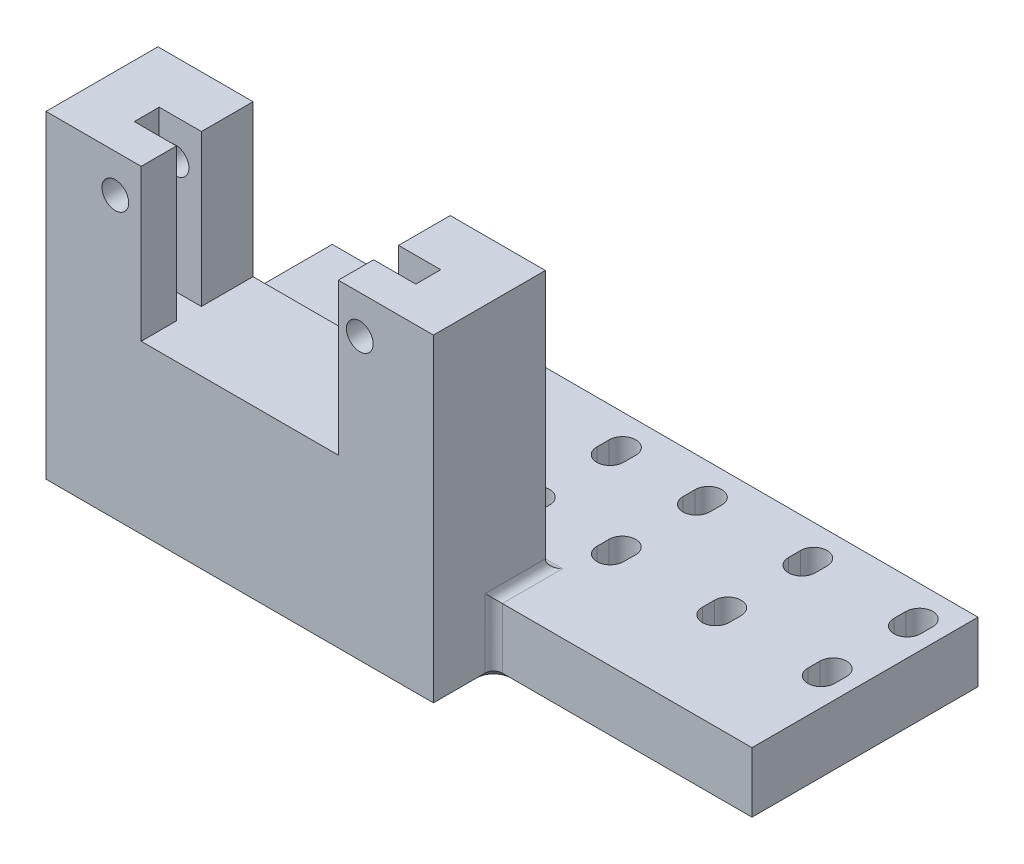
SolidWorks part; units mm, degrees
material "ABS"
ref_plane "Front Plane" through (0, 0, 0) normal (0, 0, 1) x (1, 0, 0)
ref_plane "Top Plane" through (0, 0, 0) normal (0, 1, 0) x (1, 0, 0)
ref_plane "Right Plane" through (0, 0, 0) normal (1, 0, 0) x (0, 0, -1)
sketch "Sketch1" plane through (0, 0, 0) normal (0, 1, 0) x (1, 0, 0)
  line L1 (0, 0) -> (45, 0)
  line L2 (0, 0) -> (0, 6)
  line L3 (0, 6) -> (45, 6)
  line L4 (45, 0) -> (45, 6)
  dimension "D1" = 45
  dimension "D2" = 6
extrude "Boss-Extrude1" add sketch "Sketch1" along normal blind 32
sketch "Sketch2" plane through (0, 0, 0) normal (0, 0, 1) x (1, 0, 0)
  line L0 (0, 32) -> (45, 32) construction
  line L2 (11.05, 32) -> (11.05, 14.4)
  line L3 (11.05, 14.4) -> (33.95, 14.4)
  line L4 (33.95, 32) -> (33.95, 14.4)
  line L5 (11.05, 32) -> (33.95, 32)
  line L6 (22.5, 14.4) -> (22.5, 0) construction
  line L7 (0, 0) -> (45, 0) construction
  dimension "D1" = 22.9
  dimension "D3" = 14.4
extrude "Cut-Extrude1" cut sketch "Sketch2" against normal through all
sketch "Sketch3" plane through (0, 0, 0) normal (0, -1, 0) x (1, 0, 0)
  line L0 (45, 0) -> (45, -6) construction
  line L1 (0, 0) -> (45, 0)
  line L2 (0, 0) -> (0, -24.75)
  line L3 (0, -24.75) -> (45, -24.75)
  line L4 (45, 0) -> (45, -24.75)
  dimension "D1" = 24.75
extrude "Boss-Extrude2" add sketch "Sketch3" along normal blind 6
sketch "Sketch4" plane through (45, 0, 0) normal (1, 0, 0) x (0, 0, -1)
  line L1 (24.75, 0) -> (0, 0)
  line L2 (24.75, 0) -> (24.75, -6)
  line L3 (24.75, -6) -> (0, -6)
  line L4 (0, 0) -> (0, -6)
extrude "Boss-Extrude3" add sketch "Sketch4" along normal blind 30
sketch "Sketch5" plane through (0, -6, 0) normal (0, -1, 0) x (1, 0, 0)
  line L0 (47.2888, -11.95) -> (59.5388, -11.95) construction
  line L1 (37.2888, -21.95) -> (47.2888, -21.95) construction
  line L2 (47.2888, -21.95) -> (59.5388, -21.95) construction
  line L3 (59.5388, -21.95) -> (71.7888, -21.95) construction
  line L4 (71.7888, -21.95) -> (71.7888, -11.95) construction
  line L5 (59.5388, -11.95) -> (59.5388, -21.95) construction
  line L6 (47.2888, -11.95) -> (47.2888, -21.95) construction
  line L7 (0, -24.75) -> (75, -24.75) construction
  line L8 (75, 0) -> (75, -24.75) construction
  line L9 (59.5388, -11.95) -> (71.7888, -11.95) construction
  circle A1 centre (37.2888, -21.95) radius 1.5
  circle A5 centre (47.2888, -21.95) radius 1.5
  circle A7 centre (47.2888, -11.95) radius 1.5
  circle A9 centre (59.5388, -21.95) radius 1.5
  circle A11 centre (71.7888, -21.95) radius 1.5
  circle A13 centre (71.7888, -11.95) radius 1.5
  circle A14 centre (59.5388, -11.95) radius 1.5
  dimension "D1" = 10
  dimension "D2" = 12.25
  dimension "D6" = 3
  dimension "D7" = 3.2112
  dimension "D3" = 12.25
  dimension "D4" = 2.8
  dimension "D5" = 10
extrude "Cut-Extrude2" cut sketch "Sketch5" against normal through all
sketch "Sketch6" plane through (0, 0, 0) normal (0, 0, 1) x (1, 0, 0)
  line L0 (0, -6) -> (0, 32)
  line L1 (0, 32) -> (11.05, 32)
  line L2 (11.05, 32) -> (11.05, 14.4)
  line L3 (11.05, 14.4) -> (33.95, 14.4)
  line L4 (33.95, 14.4) -> (33.95, 32)
  line L5 (33.95, 32) -> (45, 32)
  line L6 (45, 32) -> (45, -6)
  line L7 (75, -6) -> (0, -6) construction
  line L8 (45, -6) -> (-0.8534, -6)
  line M1 (45, 32) -> (33.95, 32)
  line M2 (33.95, 32) -> (33.95, 14.4)
  line M3 (33.95, 14.4) -> (11.05, 14.4)
  line M4 (11.05, 14.4) -> (11.05, 32)
  line M5 (11.05, 32) -> (0, 32)
  line M6 (0, 32) -> (0, -6)
  line M7 (0, -6) -> (75, -6)
  line M10 (45, 0) -> (45, 32)
extrude "Boss-Extrude4" add sketch "Sketch6" along normal blind 7 contours L6 M10 M1 M2 M3 M4 M5 M6 M7 region at (22.5, 9.8545, 0)
sketch "Sketch7" plane through (0, 32, 0) normal (0, 1, 0) x (1, 0, 0)
  line L1 (6.15, 0) -> (38.85, 0)
  line L2 (6.15, 0) -> (6.15, -2.9)
  line L3 (6.15, -2.9) -> (38.85, -2.9)
  line L4 (38.85, 0) -> (38.85, -2.9)
  line L5 (22.5, 6) -> (22.5, 0) construction
  line L6 (11.05, 6) -> (33.95, 6) construction
  dimension "D1" = 2.9
  dimension "D2" = 32.7
extrude "Cut-Extrude3" cut sketch "Sketch7" against normal up to surface (17.6 mm away) up to face at (22.5, 14.4, 0.5)
sketch "Sketch8" plane through (0, 0, 7) normal (0, 0, 1) x (1, 0, 0)
  line L0 (11.05, 32) -> (0, 32) construction
  line L1 (11.05, 14.4) -> (11.05, 32) construction
  line L2 (33.95, 32) -> (33.95, 14.4) construction
  circle A0 centre (8.05, 27.6) radius 1.55
  circle A1 centre (36.45, 27.6) radius 1.55
  dimension "D1" = 3.1
  dimension "D3" = 3
  dimension "D2" = 4.4
  dimension "D4" = 2.5
extrude "Cut-Extrude4" cut sketch "Sketch8" against normal through all
sketch "Sketch9" plane through (0, 0, 0) normal (0, 1, 0) x (1, 0, 0)
  line L6 (0, 6) -> (45, 6)
  line L7 (45, 6) -> (45, 0)
  line L8 (45, 0) -> (75, 0)
  line L9 (75, 0) -> (75, 24.75)
  line L10 (75, 24.75) -> (0, 24.75)
  line L11 (0, 24.75) -> (0, 6)
  line L12 (0, 6) -> (45, 6)
  line L13 (45, 6) -> (45, 0)
  line L14 (45, 0) -> (75, 0)
  line L15 (75, 0) -> (75, 24.75)
  line L16 (75, 24.75) -> (0, 24.75)
  line L17 (0, 24.75) -> (0, 6)
  circle A0 centre (71.7888, 21.95) radius 1.5 construction
  circle A1 centre (59.5388, 21.95) radius 1.5 construction
  circle A2 centre (71.7888, 11.95) radius 1.5 construction
  circle A3 centre (59.5388, 11.95) radius 1.5 construction
  circle A4 centre (47.2888, 11.95) radius 1.5 construction
  circle A5 centre (47.2888, 21.95) radius 1.5 construction
  circle A6 centre (37.2888, 21.95) radius 1.5 construction
  circle A7 centre (71.7888, 21.95) radius 1.5
  circle A8 centre (59.5388, 21.95) radius 1.5
  circle A9 centre (71.7888, 11.95) radius 1.5
  circle A10 centre (59.5388, 11.95) radius 1.5
  circle A11 centre (47.2888, 11.95) radius 1.5
  circle A12 centre (47.2888, 21.95) radius 1.5
  circle A13 centre (37.2888, 21.95) radius 1.5
  dimension "D1" = 0
extrude "Boss-Extrude5" add sketch "Sketch9" along normal blind 2
fillet "Fillet1" radius 1 3 edges at (45, -2, 0) (45, 2, -3) (22.5, 2, -6)
sketch "Sketch11" plane through (0, 0, -24.75) normal (0, 0, -1) x (-1, 0, 0)
  line L4 (0, -6) -> (0, 2)
  line L5 (0, 2) -> (-75, 2)
  line L6 (-75, 2) -> (-75, -6)
  line L7 (-75, -6) -> (0, -6)
  line L8 (0, -6) -> (0, 2)
  line L9 (0, 2) -> (-75, 2)
  line L10 (-75, 2) -> (-75, -6)
  line L11 (-75, -6) -> (0, -6)
  dimension "D1" = 0
extrude "Boss-Extrude7" add sketch "Sketch11" along normal blind 1.5
chamfer "Chamfer1" distance 1 angle 45 7 edges at (0, -6, -9.625) (75, -6, -13.125) (60.5, -6, 0) (45, -6, 4) (22.5, -6, 7) (45.2929, -6, 0.2929) (37.5, -6, -26.25)
sketch "Sketch12" plane through (0, 2, 0) normal (0, 1, 0) x (1, 0, 0)
  line L0 (37.2888, 21.2317) -> (37.2888, 22.6683) construction
  line L1 (35.7377, 21.2317) -> (35.7377, 22.6683)
  line L2 (38.84, 21.2317) -> (38.84, 22.6683)
  arc A0 (35.7377, 21.2317) -> (38.84, 21.2317) centre (37.2888, 21.2317) ccw
  arc A1 (38.84, 22.6683) -> (35.7377, 22.6683) centre (37.2888, 22.6683) ccw
  point P2 (37.2888, 21.95)
  dimension "D1" = 3.1023
  dimension "D2" = 4.5388
extrude "Cut-Extrude5" cut sketch "Sketch12" against normal through all
pattern_linear "LPattern1" count 2 spacing 10 along (0, 0, 1) of "Cut-Extrude5"
sketch "Sketch13" plane through (0, 2, 0) normal (0, 1, 0) x (1, 0, 0)
  line L0 (47.2888, 21.25) -> (47.2888, 22.65) construction
  line L1 (45.7388, 21.25) -> (45.7388, 22.65)
  line L2 (48.8388, 21.25) -> (48.8388, 22.65)
  arc A0 (45.7388, 21.25) -> (48.8388, 21.25) centre (47.2888, 21.25) ccw
  arc A1 (48.8388, 22.65) -> (45.7388, 22.65) centre (47.2888, 22.65) ccw
  point P2 (47.2888, 21.95)
  dimension "D1" = 3.1
  dimension "D2" = 4.5
extrude "Cut-Extrude6" cut sketch "Sketch13" against normal through all
pattern_linear "LPattern2" count 3 spacing 12.25 along (1, 0, 0) count 2 spacing 10 along (0, 0, 1) of "Cut-Extrude6"
